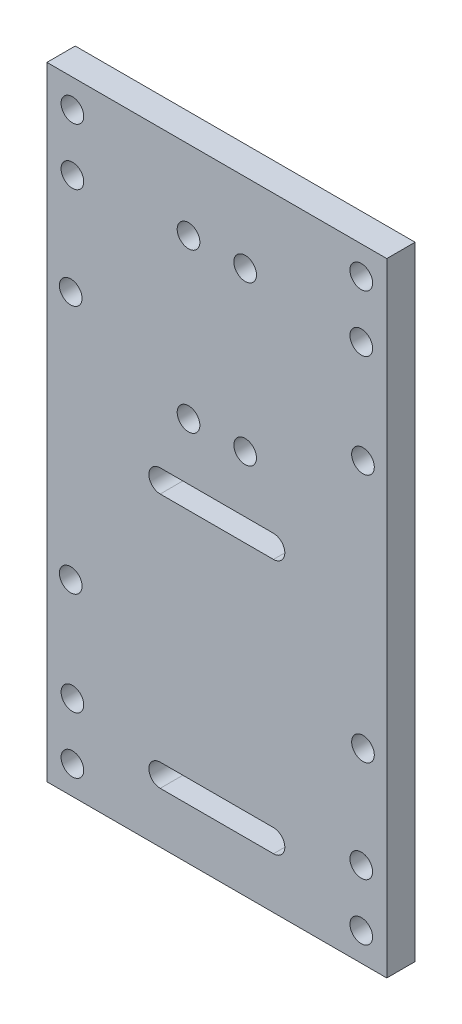
SolidWorks part; units mm, degrees
material "1060 Alloy"
ref_plane "Front Plane" through (0, 0, 0) normal (0, 0, 1) x (1, 0, 0)
ref_plane "Top Plane" through (0, 0, 0) normal (0, 1, 0) x (1, 0, 0)
ref_plane "Right Plane" through (0, 0, 0) normal (1, 0, 0) x (0, 0, -1)
sketch "Sketch1" plane through (0, 0, 0) normal (0, 0, 1) x (1, 0, 0)
  line L1 (-51.233, 91.6654) -> (24.967, 91.6654)
  line L2 (-51.233, 91.6654) -> (-51.233, -48.0346)
  line L3 (-51.233, -48.0346) -> (24.967, -48.0346)
  line L4 (24.967, 91.6654) -> (24.967, -48.0346)
  dimension "D1" = 76.2
  dimension "D2" = 139.7
extrude "Boss-Extrude1" add sketch "Sketch1" along normal blind 6.35
sketch "Sketch2" plane through (0, 0, 0) normal (0, 0, -1) x (-1, 0, 0)
  line L0 (51.233, 91.6654) -> (51.233, -48.0346) construction
  line L1 (-24.967, -48.0346) -> (-24.967, 91.6654) construction
  line L2 (-24.967, 91.6654) -> (51.233, 91.6654) construction
  line L3 (51.233, -48.0346) -> (-24.967, -48.0346) construction
  circle A0 centre (45.518, 85.3154) radius 2.54
  circle A1 centre (45.518, 72.6154) radius 2.54
  circle A2 centre (45.518, -28.9846) radius 2.54
  circle A3 centre (45.518, -41.6846) radius 2.54
  circle A4 centre (-19.252, -41.6846) radius 2.54
  circle A5 centre (-19.252, -28.9846) radius 2.54
  circle A6 centre (-19.252, 85.3154) radius 2.54
  circle A7 centre (-19.252, 72.6154) radius 2.54
  dimension "D1" = 5.08
  dimension "D2" = 5.715
  dimension "D3" = 5.715
  dimension "D4" = 12.7
  dimension "D5" = 12.7
  dimension "D6" = 6.35
  dimension "D7" = 6.35
  dimension "D8" = 12.7
  dimension "D9" = 6.35
  dimension "D10" = 6.35
  dimension "D11" = 12.7
extrude "Cut-Extrude1" cut sketch "Sketch2" against normal blind 15.24
sketch "Sketch3" plane through (0, 0, 6.35) normal (0, 0, 1) x (1, 0, 0)
  line L1 (-51.233, 91.6654) -> (-51.233, -48.0346) construction
  line L2 (24.967, 91.6654) -> (-51.233, 91.6654) construction
  circle A0 centre (-19.483, 38.3254) radius 2.54
  circle A1 centre (-6.783, 38.3254) radius 2.54
  circle A2 centre (-19.483, 73.8854) radius 2.54
  circle A3 centre (-6.783, 73.8854) radius 2.54
  dimension "D1" = 5.08
  dimension "D2" = 17.78
  dimension "D3" = 12.7
  dimension "D4" = 35.56
  dimension "D5" = 31.75
extrude "Cut-Extrude2" cut sketch "Sketch3" against normal blind 15.24
sketch "Sketch4" plane through (0, 0, 6.35) normal (0, 0, 1) x (1, 0, 0)
  line L0 (-51.233, -48.0346) -> (24.967, -48.0346) construction
  line L1 (-51.233, 91.6654) -> (-51.233, -48.0346) construction
  line L2 (24.967, -48.0346) -> (24.967, 91.6654) construction
  line L3 (24.967, 91.6654) -> (-51.233, 91.6654) construction
  circle A0 centre (-45.899, 49.7554) radius 2.54
  circle A1 centre (-45.899, -6.1246) radius 2.54
  circle A2 centre (19.633, -6.1246) radius 2.54
  circle A3 centre (19.633, 49.7554) radius 2.54
  dimension "D5" = 5.08
  dimension "D1" = 41.91
  dimension "D2" = 5.334
  dimension "D3" = 5.334
  dimension "D4" = 41.91
extrude "Cut-Extrude3" cut sketch "Sketch4" against normal blind 7.62
ref_axis "Axis1" through (-6.783, 38.3254, 0) along (0, 0, 1)
sketch "Sketch5" plane through (0, 0, 0) normal (0, 0, -1) x (-1, 0, 0)
  line L0 (0.433, 25.6254) -> (25.833, 25.6254)
  line L1 (25.833, 20.5454) -> (0.433, 20.5454)
  line L2 (-24.967, -48.0346) -> (-24.967, 91.6654) construction
  line L5 (0.433, -31.5246) -> (25.833, -31.5246)
  line L6 (25.833, -36.6046) -> (0.433, -36.6046)
  arc A0 (25.833, 25.6254) -> (25.833, 20.5454) centre (25.833, 23.0854) cw
  arc A1 (0.433, 25.6254) -> (0.433, 20.5454) centre (0.433, 23.0854) ccw
  arc A5 (25.833, -31.5246) -> (25.833, -36.6046) centre (25.833, -34.0646) cw
  arc A6 (0.433, -31.5246) -> (0.433, -36.6046) centre (0.433, -34.0646) ccw
  dimension "D1" = 2.54
  dimension "D4" = 15.24
  dimension "D6" = 2.54
  dimension "D2" = 25.4
  dimension "D3" = 25.4
  dimension "D5" = 0
  dimension "D7" = 25.4
  dimension "D8" = 57.15
extrude "Cut-Extrude4" cut sketch "Sketch5" against normal blind 7.62
